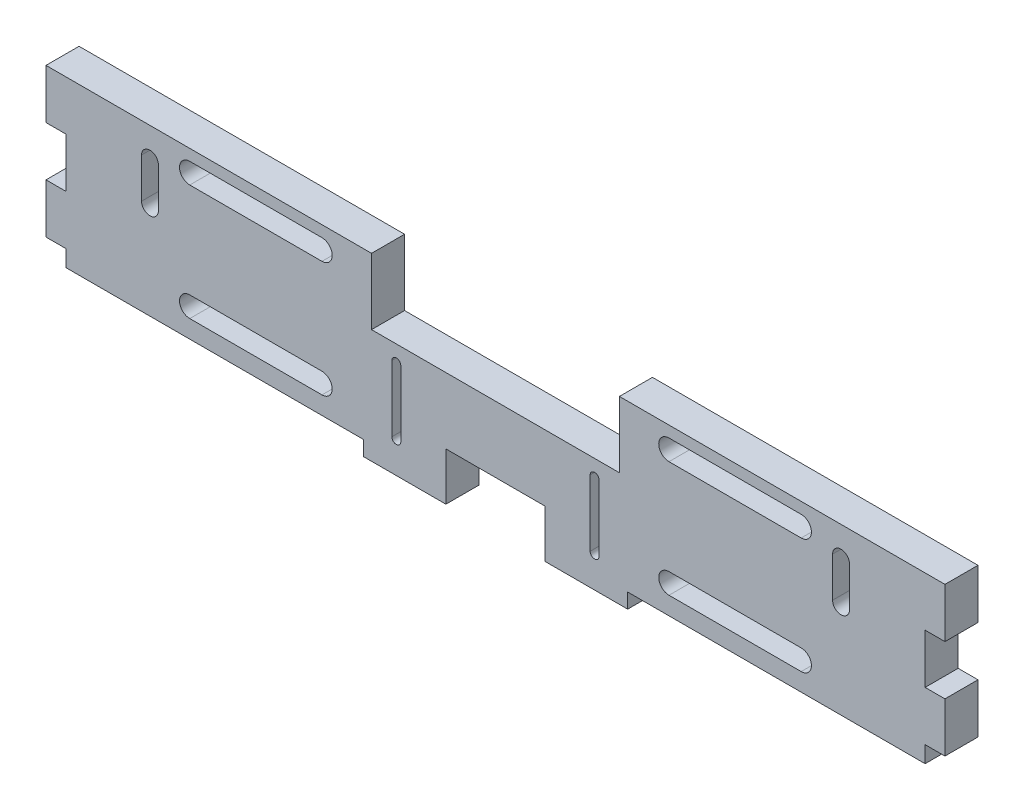
SolidWorks part; units mm, degrees
ref_plane "前基準面" through (0, 0, 0) normal (0, 0, 1) x (1, 0, 0)
ref_plane "上基準面" through (0, 0, 0) normal (0, 1, 0) x (1, 0, 0)
ref_plane "右基準面" through (0, 0, 0) normal (1, 0, 0) x (0, 0, -1)
sketch "草圖1" plane through (0, 0, 0) normal (0, 0, 1) x (1, 0, 0)
  line L0 (136, -22.5) -> (136, -7.5)
  line L1 (136, 22.5) -> (-136, 22.5)
  line L2 (130, 7.5) -> (130, -7.5)
  line L3 (130, -27.5) -> (-130, -27.5)
  line L4 (-130, 7.5) -> (-130, -7.5)
  line L5 (0, -27.5) -> (0, 22.5) construction
  line L6 (130, 0) -> (-130, 0) construction
  line L9 (-130, 7.5) -> (-136, 7.5)
  line L10 (-136, 22.5) -> (-136, 7.5)
  line L14 (-136, -22.5) -> (-136, -7.5)
  line L15 (130, -7.5) -> (136, -7.5)
  line L16 (130, 7.5) -> (136, 7.5)
  line L17 (136, 22.5) -> (136, 7.5)
  line L18 (-136, -22.5) -> (-130, -22.5)
  line L19 (-130, -22.5) -> (-130, -27.5)
  line L20 (-136, -7.5) -> (-130, -7.5)
  line L21 (130, -22.5) -> (130, -27.5)
  line L22 (130, -22.5) -> (136, -22.5)
  line L23 (-30, -22.5) -> (-30, -2.5) construction
  line L24 (-31.35, -22.5) -> (-31.35, -2.5)
  line L25 (-28.65, -22.5) -> (-28.65, -2.5)
  line L26 (30, -22.5) -> (30, -2.5) construction
  line L27 (31.35, -22.5) -> (31.35, -2.5)
  line L28 (28.65, -22.5) -> (28.65, -2.5)
  arc A0 (-31.35, -22.5) -> (-28.65, -22.5) centre (-30, -22.5) ccw
  arc A1 (-28.65, -2.5) -> (-31.35, -2.5) centre (-30, -2.5) ccw
  arc A2 (31.35, -22.5) -> (28.65, -22.5) centre (30, -22.5) cw
  arc A3 (28.65, -2.5) -> (31.35, -2.5) centre (30, -2.5) cw
  point P0 (0, 0)
  point P8 (0, 0)
  point P13 (-136, -15)
  point P14 (136, -15)
  point P24 (-30, -12.5)
  point P31 (30, -12.5)
  dimension "D8" = 1.35
  dimension "D1" = 260
  dimension "D2" = 6
  dimension "D3" = 15
  dimension "D4" = 6
  dimension "D5" = 50
  dimension "D6" = 5
  dimension "D7" = 20
  dimension "D9" = 5
  dimension "D10" = 30
extrude "填料-伸長1" add sketch "草圖1" along normal blind 10
sketch "草圖2" plane through (0, 0, 10) normal (0, 0, 1) x (1, 0, 0)
  line L0 (-92.5, 16) -> (-52.5, 16) construction
  line L1 (-92.5, 19.1) -> (-52.5, 19.1)
  line L2 (-92.5, 12.9) -> (-52.5, 12.9)
  line L3 (-92.5, -19) -> (-52.5, -19) construction
  line L4 (-92.5, -15.9) -> (-52.5, -15.9)
  line L5 (-92.5, -22.1) -> (-52.5, -22.1)
  line L6 (0, 61.8937) -> (0, -44.053) construction
  line L7 (-130, -27.5) -> (130, -27.5) construction
  line L8 (52.5, 16) -> (92.5, 16) construction
  line L9 (52.5, 19.1) -> (92.5, 19.1)
  line L10 (52.5, 12.9) -> (92.5, 12.9)
  line L11 (52.5, -19) -> (92.5, -19) construction
  line L12 (52.5, -15.9) -> (92.5, -15.9)
  line L13 (52.5, -22.1) -> (92.5, -22.1)
  arc A0 (-92.5, 19.1) -> (-92.5, 12.9) centre (-92.5, 16) ccw
  arc A1 (-52.5, 12.9) -> (-52.5, 19.1) centre (-52.5, 16) ccw
  arc A2 (-92.5, -15.9) -> (-92.5, -22.1) centre (-92.5, -19) ccw
  arc A3 (-52.5, -22.1) -> (-52.5, -15.9) centre (-52.5, -19) ccw
  arc A4 (52.5, 19.1) -> (52.5, 12.9) centre (52.5, 16) ccw
  arc A5 (92.5, 12.9) -> (92.5, 19.1) centre (92.5, 16) ccw
  arc A6 (52.5, -15.9) -> (52.5, -22.1) centre (52.5, -19) ccw
  arc A7 (92.5, -22.1) -> (92.5, -15.9) centre (92.5, -19) ccw
  point P2 (-72.5, 16)
  point P7 (-72.5, -19)
  point P22 (72.5, 16)
  point P27 (72.5, -19)
  point P37 (-95.6, -19)
  point P38 (49.4, -19)
  dimension "D3" = 3.1
  dimension "D1" = 35
  dimension "D2" = 5.4
  dimension "D4" = 40
  dimension "D6" = 145
  dimension "D5" = 2
extrude "除料-伸長1" cut sketch "草圖2" against normal through all
sketch "草圖3" plane through (0, 0, 10) normal (0, 0, 1) x (1, 0, 0)
  line L0 (0, 40.44) -> (0, -35.44) construction
  line L1 (-130, -27.5) -> (130, -27.5) construction
  line L2 (15, -17.5) -> (-15, -17.5)
  line L3 (15, -17.5) -> (15, -27.5)
  line L4 (15, -27.5) -> (-15, -27.5)
  line L5 (-15, -17.5) -> (-15, -27.5)
  line L6 (0, -27.5) -> (0, -17.5) construction
  line L7 (15, -22.5) -> (-15, -22.5) construction
  line L8 (136, 22.5) -> (-136, 22.5) construction
  line L9 (-37.5, 22.5) -> (37.5, 22.5)
  line L10 (-37.5, 22.5) -> (-37.5, 2.5)
  line L11 (-37.5, 2.5) -> (37.5, 2.5)
  line L12 (37.5, 22.5) -> (37.5, 2.5)
  circle A0 centre (0, 40.44) radius 36 construction
  point P3 (0, -22.5)
  point P16 (0, 2.5)
  dimension "D3" = 72
  dimension "D1" = 10
  dimension "D2" = 30
  dimension "D4" = 67.94
  dimension "D5" = 20
  dimension "D6" = 75
extrude "除料-伸長2" cut sketch "草圖3" against normal through all
sketch "草圖4" plane through (0, -27.5, 0) normal (0, -1, 0) x (1, 0, 0)
  line L0 (-130, 0) -> (-15, 0) construction
  line L1 (-15, 10) -> (-40, 10)
  line L2 (-15, 10) -> (-15, 0)
  line L3 (-15, 0) -> (-40, 0)
  line L4 (-40, 10) -> (-40, 0)
  line L5 (0, 39.3448) -> (0, -9.8344) construction
  line L6 (15, 0) -> (40, 0)
  line L7 (40, 10) -> (40, 0)
  line L8 (15, 10) -> (40, 10)
  line L9 (15, 10) -> (15, 0)
  dimension "D1" = 25
  dimension "D2" = 30
extrude "填料-伸長2" add sketch "草圖4" along normal blind 4.5
sketch "草圖5" plane through (0, 0, 10) normal (0, 0, 1) x (1, 0, 0)
  line L0 (-46.5, -27.5) -> (-98.5, -27.5) construction
  line L1 (-46.5, -27.5) -> (-46.5, 24.5) construction
  line L2 (-46.5, 24.5) -> (-98.5, 24.5) construction
  line L3 (-98.5, -27.5) -> (-98.5, 24.5) construction
  line L4 (-112.3, 7.4) -> (-99.5, 7.4) construction
  line L5 (-112.3, 20) -> (-99.5, 20) construction
  line L6 (-112.3, 20) -> (-112.3, -5.2) construction
  line L7 (-112.3, -5.2) -> (-99.5, -5.2) construction
  line L8 (-99.5, 20) -> (-99.5, -5.2) construction
  line L9 (-107.1, 13.45) -> (-107.1, 1.35)
  line L10 (-102, 1.35) -> (-102, 13.45)
  line L11 (0, 35.1152) -> (0, -35.1152) construction
  line L12 (107.1, 13.45) -> (107.1, 1.35)
  line L13 (102, 1.35) -> (102, 13.45)
  line L14 (-130, -27.5) -> (-40, -27.5) construction
  line L15 (-136, 22.5) -> (-136, 7.5) construction
  arc A0 (-102, 13.45) -> (-107.1, 13.45) centre (-104.55, 13.45) ccw
  arc A1 (-107.1, 1.35) -> (-102, 1.35) centre (-104.55, 1.35) ccw
  arc A2 (102, 13.45) -> (107.1, 13.45) centre (104.55, 13.45) cw
  arc A3 (107.1, 1.35) -> (102, 1.35) centre (104.55, 1.35) cw
  point P12 (-104.55, 3.9)
  point P13 (-104.55, 10.9)
  point P16 (-104.55, 16)
  point P18 (-107.1, 13.45)
  point P21 (-102, 13.45)
  dimension "D5" = 5.1
  dimension "D1" = 52
  dimension "D2" = 52
  dimension "D3" = 12.8
  dimension "D4" = 7
  dimension "D6" = 4
  dimension "D7" = 2.5
  dimension "D8" = 1
  dimension "D9" = 12.1
  dimension "D10" = 47.5
  dimension "D11" = 37.5
extrude "除料-伸長3" cut sketch "草圖5" against normal through all
